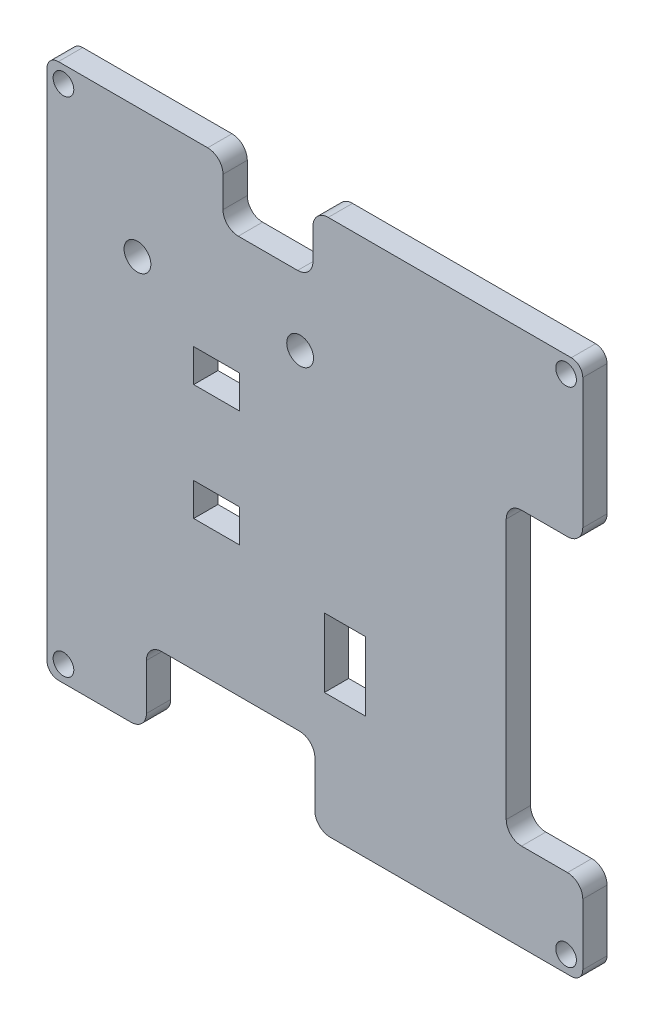
SolidWorks part; units mm, degrees
ref_plane "Front Plane" through (0, 0, 0) normal (0, 0, 1) x (1, 0, 0)
ref_plane "Top Plane" through (0, 0, 0) normal (0, 1, 0) x (1, 0, 0)
ref_plane "Right Plane" through (0, 0, 0) normal (1, 0, 0) x (0, 0, -1)
sketch "Sketch1" plane through (0, 0, 0) normal (0, 0, 1) x (1, 0, 0)
  line L1 (-35, 35) -> (35, 35)
  line L2 (-35, 35) -> (-35, -35)
  line L3 (-35, -35) -> (35, -35)
  line L4 (35, 35) -> (35, -35)
  line L5 (-35, 35) -> (35, -35) construction
  line L6 (-35, -35) -> (35, 35) construction
  circle A0 centre (-32.84, 32.82) radius 1.35
  circle A2 centre (-32.84, -32.84) radius 1.35
  circle A3 centre (32.82, -32.84) radius 1.35
  circle A4 centre (32.82, 32.82) radius 1.35
  point P0 (0, 0)
  dimension "D5" = 2.7
  dimension "D7" = 2.7
  dimension "D9" = 2.7
  dimension "D12" = 2.7
  dimension "D1" = 70
  dimension "D2" = 70
  dimension "D3" = 2.16
  dimension "D4" = 2.16
  dimension "D6" = 65.66
  dimension "D8" = 65.66
  dimension "D10" = 65.66
  dimension "D11" = 65.66
extrude "Boss-Extrude1" add sketch "Sketch1" along normal blind 3.175
fillet "Fillet1" radius 1.5 4 edges at (35, 35, 1.5875) (35, -35, 1.5875) (-35, -35, 1.5875) (-35, 35, 1.5875)
sketch "Sketch2" plane through (0, 0, 0) normal (0, 0, -1) x (-1, 0, 0)
  line L0 (0, 0) -> (35, 0) construction
  line L1 (35, 33.5) -> (35, -33.5) construction
  line L2 (0, 0) -> (0, 35) construction
  line L3 (-33.5, 35) -> (33.5, 35) construction
  line L4 (-25, -23.5) -> (-25, 14.5)
  line L18 (-35, 14.5) -> (-25, 14.5)
  line L19 (-35, -33.5) -> (-35, 33.5) construction
  line L25 (-25, -23.5) -> (-35, -23.5)
  line L26 (-35, 14.5) -> (-35, -23.5)
  line L27 (-33.5, 35) -> (33.5, 35) construction
  dimension "D1" = 20.5
  dimension "D2" = 38
  dimension "D5" = 10
  dimension "D6" = 10
extrude "Cut-Extrude1" cut sketch "Sketch2" against normal through all both and the other way through all
fillet "Fillet2" radius 2 4 edges at (35, -23.5, 1.5875) (35, 14.5, 1.5875) (25, 14.5, 1.5875) (25, -23.5, 1.5875)
sketch "Sketch3" plane through (0, 0, 0) normal (0, 0, -1) x (-1, 0, 0)
  line L0 (33.5, -35) -> (-33.5, -35) construction
  line L1 (22, -35) -> (0, -35)
  line L2 (22, -35) -> (22, -25)
  line L3 (22, -25) -> (0, -25)
  line L4 (0, -35) -> (0, -25)
  line L5 (-33.5, 35) -> (33.5, 35) construction
  line L6 (12, 35) -> (0.25, 35)
  line L7 (12, 35) -> (12, 27)
  line L8 (12, 27) -> (0.25, 27)
  line L9 (0.25, 35) -> (0.25, 27)
  line L10 (35, 33.5) -> (35, -33.5) construction
  line L11 (35, 33.5) -> (35, -33.5) construction
  line L13 (-1.25, -10) -> (-6.6, -10)
  line L14 (-1.25, -10) -> (-1.25, -19)
  line L15 (-1.25, -19) -> (-6.6, -19)
  line L16 (-6.6, -10) -> (-6.6, -19)
  dimension "D1" = 11.75
  dimension "D2" = 23
  dimension "D3" = 8
  dimension "D4" = 13
  dimension "D5" = 22
  dimension "D6" = 10
  dimension "D7" = 5.35
  dimension "D8" = 9
  dimension "D9" = 45
  dimension "D10" = 36.25
extrude "Cut-Extrude2" cut sketch "Sketch3" against normal through all both and the other way through all
fillet "Fillet3" radius 2 8 edges at (0, -35, 1.5875) (-22, -35, 1.5875) (-22, -25, 1.5875) (0, -25, 1.5875) (-12, 27, 1.5875) (-0.25, 27, 1.5875) (-0.25, 35, 1.5875) (-12, 35, 1.5875)
sketch "Sketch4" plane through (0, 0, 0) normal (0, 0, -1) x (-1, 0, 0)
  line L0 (23.174, 18.0966) -> (1.924, 18.0966) construction
  line L2 (15.824, 11.5966) -> (9.824, 11.5966)
  line L3 (15.824, 11.5966) -> (15.824, 7.2966)
  line L4 (15.824, 7.2966) -> (9.824, 7.2966)
  line L5 (9.824, 11.5966) -> (9.824, 7.2966)
  line L6 (15.824, -3.5534) -> (9.824, -3.5534)
  line L7 (15.824, -3.5534) -> (15.824, -7.8534)
  line L8 (15.824, -7.8534) -> (9.824, -7.8534)
  line L9 (9.824, -3.5534) -> (9.824, -7.8534)
  circle A0 centre (23.174, 18.0966) radius 1.75
  circle A1 centre (1.924, 18.0966) radius 1.75
  point P12 (0, 0)
  point P13 (19.7891, 22.3929)
  point P14 (23.174, 18.0966)
  dimension "D2" = 3.5
  dimension "D3" = 3.5
  dimension "D1" = 21.25
  dimension "D4" = 6.5
  dimension "D5" = 7.35
  dimension "D6" = 6
  dimension "D7" = 4.3
  dimension "D8" = 6
  dimension "D9" = 4.3
  dimension "D10" = 10.85
extrude "Cut-Extrude3" cut sketch "Sketch4" against normal through all both and the other way through all
